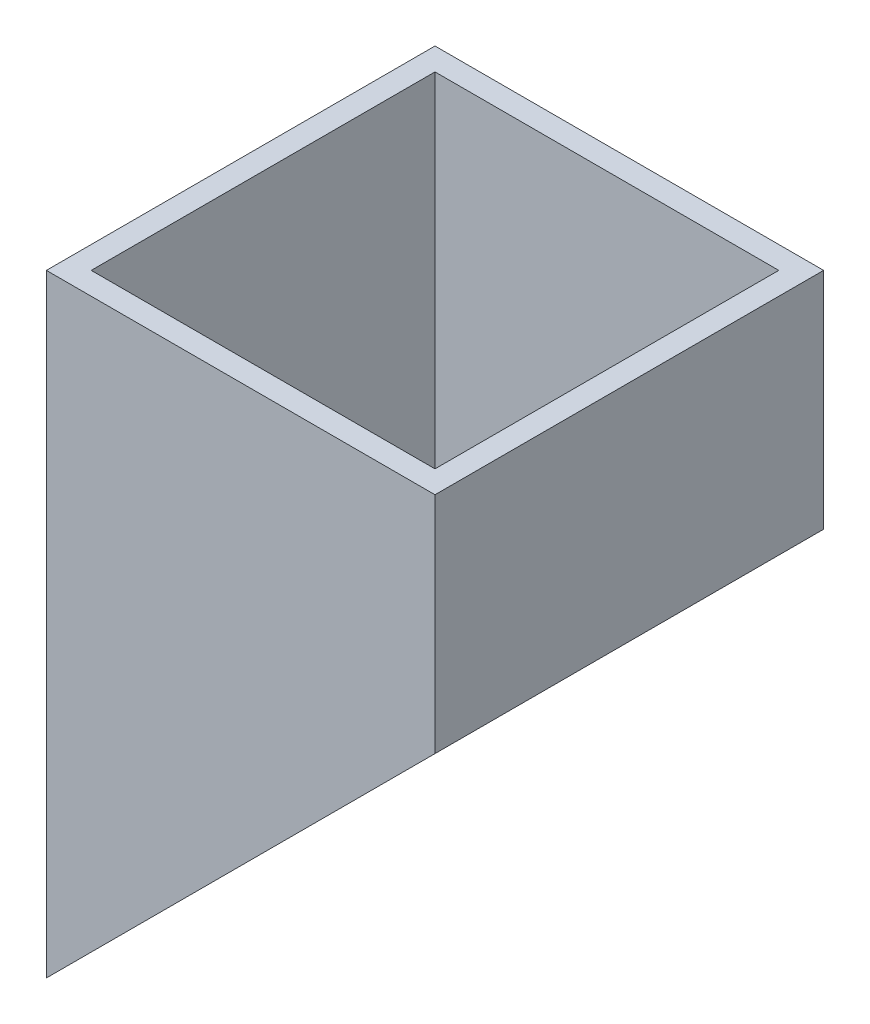
SolidWorks part; units mm, degrees
ref_plane "Alzado" through (0, 0, 0) normal (0, 0, 1) x (1, 0, 0)
ref_plane "Planta" through (0, 0, 0) normal (0, 1, 0) x (1, 0, 0)
ref_plane "Vista lateral" through (0, 0, 0) normal (1, 0, 0) x (0, 0, -1)
sketch "Croquis1" plane through (0, 0, 0) normal (0, 1, 0) x (1, 0, 0)
  line L1 (0, 0) -> (52, 0)
  line L2 (0, 0) -> (0, 52)
  line L3 (0, 52) -> (52, 52)
  line L4 (52, 0) -> (52, 52)
  dimension "D1" = 52
  dimension "D2" = 52
extrude "Saliente-Extruir1" add sketch "Croquis1" along normal blind 30
sketch "Croquis2" plane through (0, 0, 0) normal (0, 0, 1) x (1, 0, 0)
  line L0 (0, 0) -> (0, -52)
  line L1 (0, -52) -> (52, 0)
  line L2 (52, 0) -> (0, 0)
  dimension "D1" = 45
extrude "Saliente-Extruir2" add sketch "Croquis2" against normal up to surface (52 mm away) up to face at (26, 15, -52)
shell "Vaciado4" thickness 3 removed face at (26, 30, -26) removed face at (26, -26, -26)
